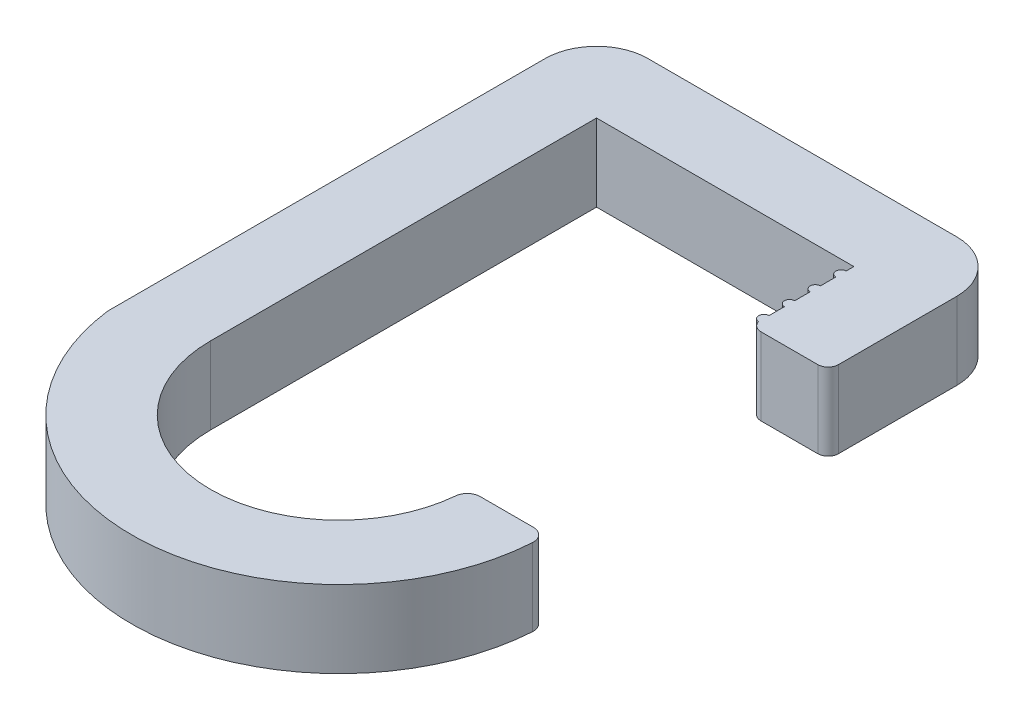
SolidWorks part; units mm, degrees
ref_plane "Front Plane" through (0, 0, 0) normal (0, 0, 1) x (1, 0, 0)
ref_plane "Top Plane" through (0, 0, 0) normal (0, 1, 0) x (1, 0, 0)
ref_plane "Right Plane" through (0, 0, 0) normal (1, 0, 0) x (0, 0, -1)
sketch "Sketch1" plane through (0, 0, 0) normal (0, 1, 0) x (1, 0, 0)
  line L0 (65, -75) -> (80.3113, -75)
  line L1 (15, 0) -> (65, 0)
  line L2 (0, 0) -> (0, 15)
  line L3 (0, 15) -> (80, 15)
  line L4 (80, 0) -> (80, 15)
  line L6 (80, 0) -> (80, -20)
  line L7 (80, -20) -> (65, -20)
  line L8 (65, 0) -> (65, -1.5)
  line L10 (0, 0) -> (0, -50)
  line L12 (15, 0) -> (15, -50)
  line L14 (0, -50) -> (0, -80)
  line L16 (15, -50) -> (15, -75)
  line L17 (65, -3.5) -> (65, -6.5)
  line L18 (65, -8.5) -> (65, -11.5)
  line L19 (65, -13.5) -> (65, -16.5)
  line L20 (65, -18.5) -> (65, -20)
  arc A0 (15, -75) -> (65, -75) centre (40, -75) ccw
  arc A1 (0, -80) -> (80.3113, -75) centre (40, -75) ccw
  arc A2 (65, -1.5) -> (65, -3.5) centre (65, -2.5) ccw
  arc A3 (65, -6.5) -> (65, -8.5) centre (65, -7.5) ccw
  arc A4 (65, -11.5) -> (65, -13.5) centre (65, -12.5) ccw
  arc A5 (65, -16.5) -> (65, -18.5) centre (65, -17.5) ccw
  dimension "D8" = 2
  dimension "D1" = 80
  dimension "D2" = 15
  dimension "D3" = 15
  dimension "D4" = 20
  dimension "D6" = 15
  dimension "D7" = 30
  dimension "D9" = 2.5
  dimension "D10" = 4
extrude "Boss-Extrude1" add sketch "Sketch1" along normal blind 15
fillet "Fillet1" radius 10 2 edges at (80, 7.5, -15) (0, 7.5, -15)
fillet "Fillet3" radius 2 2 edges at (80, 7.5, 20) (65, 7.5, 20)
fillet "Fillet6" radius 2.5 2 edges at (80.3113, 7.5, 75) (65, 7.5, 75)
